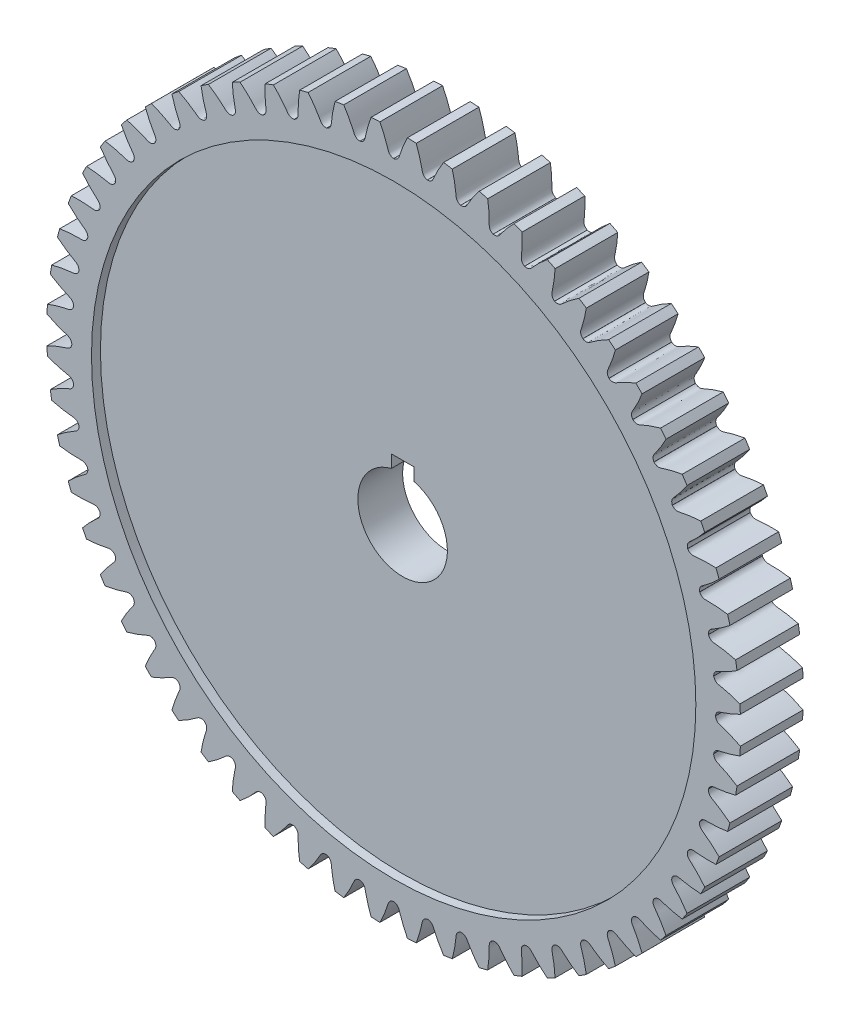
SolidWorks part; units mm, degrees
ref_plane "前视基准面" through (0, 0, 0) normal (0, 0, 1) x (1, 0, 0)
ref_plane "上视基准面" through (0, 0, 0) normal (0, 1, 0) x (1, 0, 0)
ref_plane "右视基准面" through (0, 0, 0) normal (1, 0, 0) x (0, 0, -1)
sketch "草图1" plane through (0, 0, 0) normal (0, 0, 1) x (1, 0, 0)
  circle A0 centre (0, 0) radius 77.5
extrude "凸台-拉伸1" add sketch "草图1" along normal blind 14
ref_axis "基准轴1" through (0, 0, 14) along (0, 0, -1)
sketch "草图2" plane through (0, 0, 0) normal (0, 0, 1) x (1, 0, 0)
  line L0 (0, 0) -> (0, 77.5) construction
  circle A0 centre (0, 0) radius 77.5 construction
  arc A1 (0.01, 71.8749) -> (-0.01, 71.8749) centre (0, 0) ccw
  arc A2 (10.5214, 87.663) -> (-10.5214, 87.663) centre (0, 0) ccw
  spline S0 degree 3 poles (0.01, 71.8749) (1.0723, 72.0409) (1.2384, 72.9103) (1.5597, 73.8756) (1.7101, 74.3079) (1.8796, 74.7631) (2.0684, 75.2412) (2.2776, 75.7413) (2.5082, 76.263) (2.7611, 76.8055) (3.0371, 77.3682) (3.3373, 77.9503) (3.6625, 78.5511) (4.0135, 79.1698) (4.3913, 79.8055) (4.7965, 80.4576) (5.2301, 81.125) (5.6927, 81.807) (6.1852, 82.5026) (6.7082, 83.2109) (7.2625, 83.9309) (7.8487, 84.6617) (8.4675, 85.4023) (9.3492, 86.4155) (10.0429, 87.1655) (10.5214, 87.663) knots 0 0 0 0 0.113064 0.135455 0.159317 0.184648 0.21145 0.239722 0.269464 0.300676 0.333358 0.36751 0.403132 0.440224 0.478787 0.518819 0.560322 0.603295 0.647738 0.693651 0.741034 0.789887 0.84021 0.892003 1 1 1 1
  spline S1 degree 3 poles (-0.01, 71.8749) (-1.0723, 72.0409) (-1.2384, 72.9103) (-1.5597, 73.8756) (-1.7101, 74.3079) (-1.8796, 74.7631) (-2.0684, 75.2412) (-2.2776, 75.7413) (-2.5082, 76.263) (-2.7611, 76.8055) (-3.0371, 77.3682) (-3.3373, 77.9503) (-3.6625, 78.5511) (-4.0135, 79.1698) (-4.3913, 79.8055) (-4.7965, 80.4576) (-5.2301, 81.125) (-5.6927, 81.807) (-6.1852, 82.5026) (-6.7082, 83.2109) (-7.2625, 83.9309) (-7.8487, 84.6617) (-8.4675, 85.4023) (-9.3492, 86.4155) (-10.0429, 87.1655) (-10.5214, 87.663) knots 0 0 0 0 0.113064 0.135455 0.159317 0.184648 0.21145 0.239722 0.269464 0.300676 0.333358 0.36751 0.403132 0.440224 0.478787 0.518819 0.560322 0.603295 0.647738 0.693651 0.741034 0.789887 0.84021 0.892003 1 1 1 1
extrude "切除-拉伸1" cut sketch "草图2" along normal through all
pattern_circular "阵列(圆周)1" count 60 over 360 about axis through (0, 0, 14) along (0, 0, -1) of "切除-拉伸1"
sketch "草图3" plane through (0, 0, 0) normal (0, 0, 1) x (1, 0, 0)
  circle A0 centre (0, 0) radius 75 construction
  dimension "Dn" = 150
sketch "草图4" plane through (0, 0, 14) normal (0, 0, 1) x (1, 0, 0)
  point P0 (0, 0)
sketch "草图6" plane through (0, 0, 14) normal (0, 0, 1) x (1, 0, 0)
  line L1 (-2.5, 12.5) -> (2.5, 12.5)
  line L2 (-2.5, 12.5) -> (-2.5, 9.6825)
  line L4 (2.5, 12.5) -> (2.5, 9.6825)
  line L5 (0, 11.5) -> (0, 12.5) construction
  arc A0 (-2.5, 9.6825) -> (2.5, 9.6825) centre (0, 0) ccw
  point P3 (0, 10)
  dimension "D1" = 20
  dimension "D2" = 5
  dimension "D3" = 12.5
extrude "切除-拉伸2" cut sketch "草图6" against normal blind 50
sketch "草图7" plane through (0, 0, 0) normal (0, 0, -1) x (-1, 0, 0)
  circle A0 centre (0, 0) radius 67.5
  dimension "D1" = 135
extrude "切除-拉伸3" cut sketch "草图7" against normal blind 2
sketch "草图8" plane through (0, 0, 14) normal (0, 0, 1) x (1, 0, 0)
  circle A0 centre (0, 0) radius 67.5
  dimension "D1" = 135
extrude "切除-拉伸4" cut sketch "草图8" against normal blind 2
